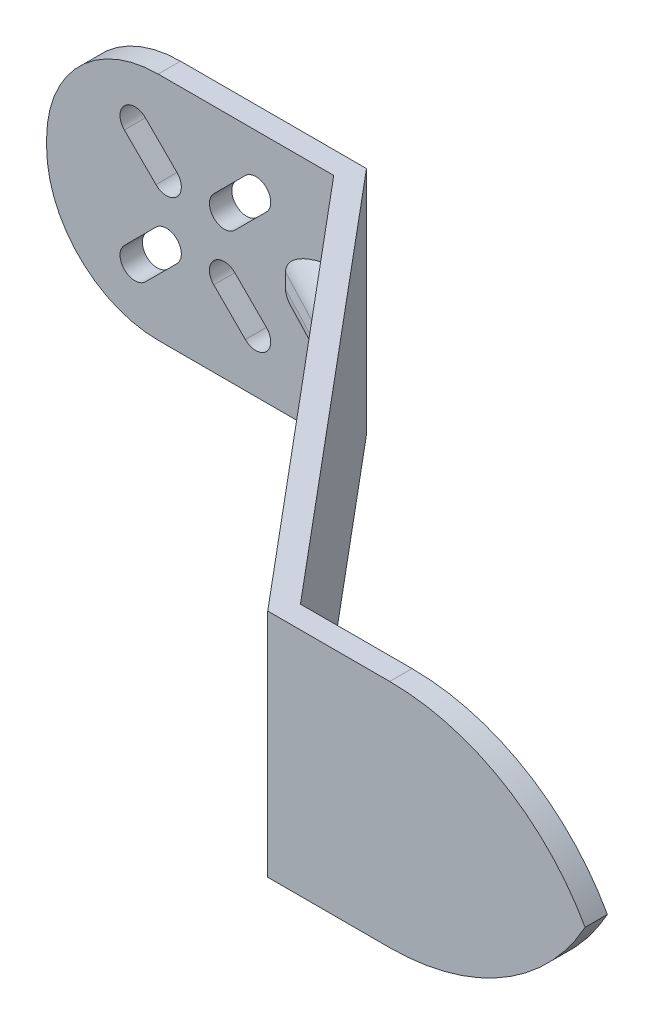
SolidWorks part; units mm, degrees
ref_plane "Alzado" through (0, 0, 0) normal (0, 0, 1) x (1, 0, 0)
ref_plane "Planta" through (0, 0, 0) normal (0, 1, 0) x (1, 0, 0)
ref_plane "Vista lateral" through (0, 0, 0) normal (1, 0, 0) x (0, 0, -1)
sketch "Croquis2" plane through (0, 0, 0) normal (0, 1, 0) x (1, 0, 0)
  line L0 (-84.8818, 58.1552) -> (-84.8818, 55.1552)
  line L1 (-84.8818, 55.1552) -> (-46.2807, 55.1552)
  line L2 (-46.2807, 55.1552) -> (0, 0)
  line L3 (0, 0) -> (46.3989, 0)
  line L4 (46.3989, 0) -> (46.3989, 3)
  line L5 (46.3989, 3) -> (1.3989, 3)
  line L6 (1.3989, 3) -> (-44.8818, 58.1552)
  line L7 (-44.8818, 58.1552) -> (-84.8818, 58.1552)
  dimension "D1" = 3
  dimension "D2" = 3
  dimension "D3" = 3
  dimension "D4" = 40
  dimension "D5" = 45
  dimension "D6" = 72
  dimension "D7" = 130
extrude "Saliente-Extruir2" add sketch "Croquis2" along normal blind 31
sketch "Croquis3" plane through (0, 0, -58.1552) normal (0, 0, -1) x (-1, 0, 0)
  line L0 (84.8818, 15.5) -> (44.8818, 15.5) construction
  line L3 (84.8818, 31) -> (84.8818, 0) construction
  line L6 (73.0135, 7.3683) -> (56.7501, 23.6317) construction
  line L9 (44.8818, 31) -> (44.8818, 0) construction
  line L12 (73.0135, 23.6317) -> (56.7501, 7.3683) construction
  line L13 (73.0135, 23.6317) -> (56.7501, 7.3683) construction
  line L16 (73.0135, 7.3683) -> (56.7501, 23.6317) construction
  line L19 (56.7501, 23.6317) -> (60.9927, 19.3891) construction
  line L20 (58.1643, 25.0459) -> (62.4069, 20.8033)
  line L21 (55.3358, 22.2175) -> (59.5785, 17.9749)
  line L22 (73.0135, 7.3683) -> (68.7709, 11.6109) construction
  line L23 (71.5993, 5.9541) -> (67.3567, 10.1967)
  line L24 (74.4277, 8.7825) -> (70.1851, 13.0251)
  line L25 (73.0135, 23.6317) -> (68.7709, 19.3891) construction
  line L26 (74.4277, 22.2175) -> (70.1851, 17.9749)
  line L27 (71.5993, 25.0459) -> (67.3567, 20.8033)
  line L28 (56.7501, 7.3683) -> (60.9927, 11.6109) construction
  line L29 (55.3358, 8.7825) -> (59.5785, 13.0251)
  line L30 (58.1643, 5.9541) -> (62.4069, 10.1967)
  arc A12 (58.1643, 25.0459) -> (55.3358, 22.2175) centre (56.7501, 23.6317) ccw
  arc A13 (59.5785, 17.9749) -> (62.4069, 20.8033) centre (60.9927, 19.3891) ccw
  arc A14 (71.5993, 5.9541) -> (74.4277, 8.7825) centre (73.0135, 7.3683) ccw
  arc A15 (70.1851, 13.0251) -> (67.3567, 10.1967) centre (68.7709, 11.6109) ccw
  arc A16 (74.4277, 22.2175) -> (71.5993, 25.0459) centre (73.0135, 23.6317) ccw
  arc A17 (67.3567, 20.8033) -> (70.1851, 17.9749) centre (68.7709, 19.3891) ccw
  arc A18 (55.3358, 8.7825) -> (58.1643, 5.9541) centre (56.7501, 7.3683) ccw
  arc A19 (62.4069, 10.1967) -> (59.5785, 13.0251) centre (60.9927, 11.6109) ccw
  point P6 (64.8818, 15.5)
  point P8 (64.8818, 15.5)
  point P9 (0, 0)
  point P12 (64.8818, 15.5)
  point P14 (70.8922, 21.5104)
  point P19 (58.8714, 21.5104)
  point P25 (70.8922, 9.4896)
  point P33 (58.8714, 9.4896)
  point P39 (0, 0)
  point P40 (68.2408, 14.4917)
  point P41 (64.2006, 13.8243)
  dimension "D5" = 6
  dimension "D6" = 6
  dimension "D7" = 4
  dimension "D8" = 4
  dimension "D1" = 45
  dimension "D2" = 45
  dimension "D3" = 4
  dimension "D4" = 23
  dimension "D9" = 6
  dimension "D10" = 4
  dimension "D11" = 6
  dimension "D12" = 23
extrude "Cortar-Extruir1" cut sketch "Croquis3" against normal blind 10
fillet "Redondeo4" radius 15 2 edges at (-84.8818, 31, -56.6552) (-84.8818, 0, -56.6552)
fillet "Redondeo7" radius 30 2 edges at (46.3989, 0, -1.5) (46.3989, 31, -1.5)
ref_plane "Plano1" through (0, 15.5, 0) normal (0, 1, 0) x (1, 0, 0)
sketch "Croquis4" plane through (0, 15.5, 0) normal (0, 1, 0) x (1, 0, 0)
  line L0 (-8.1086, 14.3306) -> (16.3989, 3)
  line L1 (1.3989, 3) -> (-44.8818, 58.1552) construction
  line L2 (-52.7604, 55.1552) -> (-41.2349, 49.1418)
  line L3 (-46.2807, 55.1552) -> (0, 0) construction
  line L4 (-69.8818, 55.1552) -> (-46.2807, 55.1552) construction
  line L5 (16.3989, 3) -> (1.3989, 3) construction
  line L6 (-52.7604, 55.1552) -> (-46.2807, 55.1552)
  line L7 (-46.2807, 55.1552) -> (-41.2349, 49.1418)
  line L8 (-8.1086, 14.3306) -> (1.3989, 3)
  line L9 (1.3989, 3) -> (16.3989, 3)
  dimension "D1" = 13
  dimension "D2" = 6.4797
  dimension "D3" = 27
extrude "Saliente-Extruir3" add sketch "Croquis4" along normal mid plane 10
fillet "Redondeo8" radius 4 1 edges at (4.1452, 20.5, -8.6653)
fillet "Redondeo9" radius 4 1 edges at (4.1452, 10.5, -8.6653)
fillet "Redondeo11" radius 4 2 edges at (-46.9976, 10.5, -52.1485) (-46.9976, 20.5, -52.1485)
